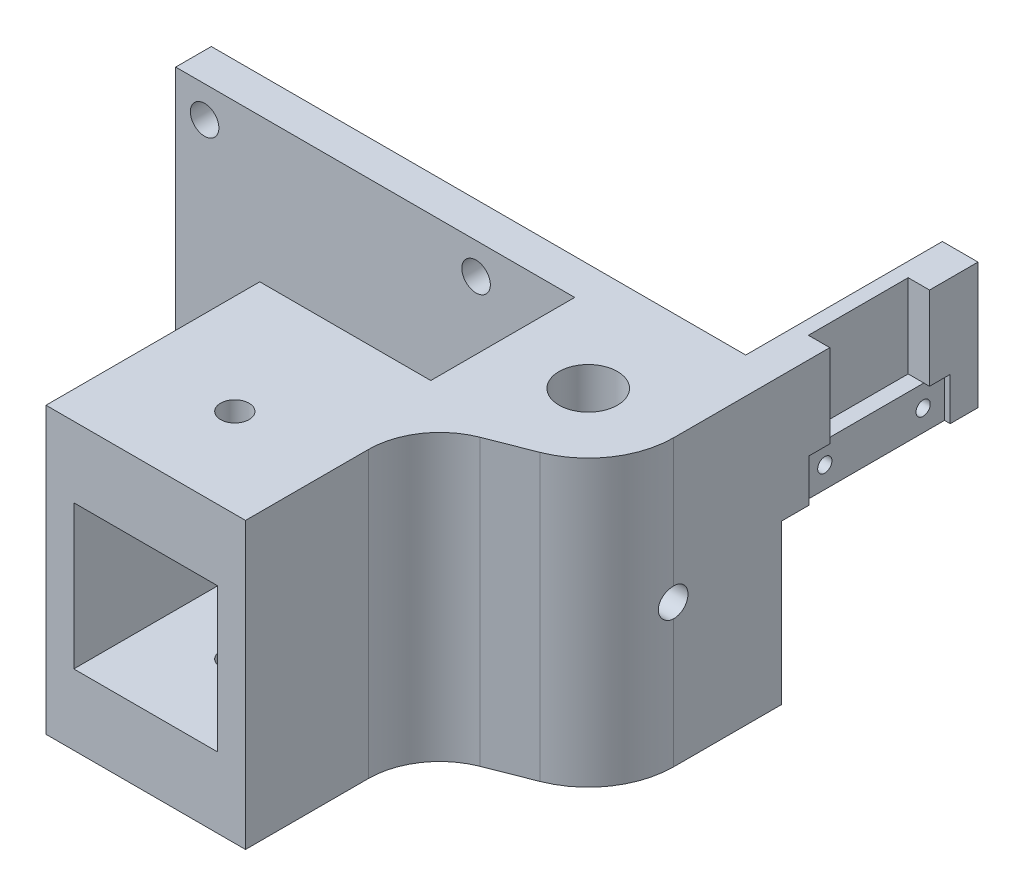
SolidWorks part; units mm, degrees
ref_plane "Front Plane" through (0, 0, 0) normal (0, 0, 1) x (1, 0, 0)
ref_plane "Top Plane" through (0, 0, 0) normal (0, 1, 0) x (1, 0, 0)
ref_plane "Right Plane" through (0, 0, 0) normal (1, 0, 0) x (0, 0, -1)
sketch "Sketch1" plane through (0, 0, 0) normal (0, 1, 0) x (1, 0, 0)
  line L0 (-32, 55.2) -> (-32, 50.2)
  line L1 (-32, 50.2) -> (24, 50.2)
  line L2 (24, 50.2) -> (24, 30)
  line L3 (24, 30) -> (0, 30)
  line L4 (0, 30) -> (0, 0)
  line L5 (0, 0) -> (28, 0)
  line L6 (28, 0) -> (28, 17.2586)
  line L7 (28, 55.2) -> (-32, 55.2)
  line L9 (40.3722, 28.9249) -> (34.3565, 26.5712)
  line L10 (28, 55.2) -> (43, 55.2)
  line L11 (43, 55.2) -> (43, 82.8)
  line L12 (43, 82.8) -> (48, 82.8)
  line L13 (48, 82.8) -> (48, 40.1)
  circle A1 centre (36, 40.1) radius 4.1
  arc A2 (48, 40.1) -> (40.3722, 28.9249) centre (36, 40.1) cw
  arc A3 (28, 17.2586) -> (34.3565, 26.5712) centre (38, 17.2586) cw
  point P18 (24, 40.1)
  point P36 (43, 69)
  dimension "D6" = 8.2
  dimension "D7" = 5
  dimension "D10" = 10
  dimension "D1" = 5
  dimension "D2" = 4
  dimension "D3" = 30
  dimension "D4" = 20.2
  dimension "D5" = 28
  dimension "D8" = 8
  dimension "D9" = 19
  dimension "D11" = 13.8
extrude "Boss-Extrude1" add sketch "Sketch1" along normal blind 40 contours L6 A1 L9 | L6 L7 L0 L1 L2 L3 L4 L5 region at (-2, 0, -54.0487)
sketch "Sketch2" plane through (0, 0, 0) normal (0, 0, 1) x (1, 0, 0)
  line L0 (14, 30.1) -> (14, 9.9) construction
  line L1 (3.9, 30.1) -> (24.1, 30.1)
  line L2 (3.9, 30.1) -> (3.9, 9.9)
  line L3 (3.9, 9.9) -> (24.1, 9.9)
  line L4 (24.1, 30.1) -> (24.1, 9.9)
  line L5 (24.1, 20) -> (3.9, 20) construction
  line L8 (0, 40) -> (0, 0) construction
  line L9 (28, 40) -> (28, 0) construction
  line L10 (0, 40) -> (0, 0) construction
  line L11 (0, 40) -> (0, 0)
  point P10 (0, 20)
  dimension "D1" = 20.2
extrude "Cut-Extrude1" cut sketch "Sketch2" against normal blind 25 contours L4 L1 L2 L3 region at (14, 20, 0)
sketch "Sketch3" plane through (0, 40, 0) normal (0, 1, 0) x (1, 0, 0)
  line L1 (3.9, 25) -> (24.1, 25) construction
  line L2 (14, 25) -> (14, 0) construction
  line L4 (3.9, 25) -> (24.1, 25)
  line L5 (0, 0) -> (28, 0) construction
  circle A0 centre (14, 12.5) radius 2
  dimension "D1" = 4
extrude "Cut-Extrude2" cut sketch "Sketch3" against normal through all contours A0
sketch "Sketch4" plane through (0, 0, -55.2) normal (0, 0, -1) x (-1, 0, 0)
  line L0 (32, 20) -> (-24.602, 20) construction
  line L1 (32, 40) -> (32, 0) construction
  line L2 (-24.602, 40) -> (-24.602, 0) construction
  line L3 (-24, 40) -> (-24, 0) construction
  line L4 (-24, 40) -> (-24, 0)
  circle A0 centre (-10.16, 35.62) radius 2
  circle A1 centre (27.94, 35.62) radius 2
  circle A3 centre (27.94, 4.38) radius 2
  circle A5 centre (-10.16, 4.38) radius 2
  dimension "D5" = 4
  dimension "D3" = 31.24
  dimension "D4" = 38.1
  dimension "D6" = 13.84
  dimension "D1" = 2
  dimension "D2" = 2
extrude "Cut-Extrude3" cut sketch "Sketch4" against normal up to surface (5 mm away) contours A5 | A1 | A3 | A0 up to face at (-4, 20, -50.2)
sketch "Sketch5" plane through (48, 0, 0) normal (1, 0, 0) x (0, 0, -1)
  line L0 (55.2, 40) -> (55.2, 0) construction
  line L1 (55.2, 40) -> (55.2, 0)
  line L2 (55.2, 20) -> (82.8, 20) construction
  line L3 (40.1, 40) -> (40.1, 0) construction
  line L4 (82.8, 40) -> (82.8, 0) construction
  line L6 (76, 22.3) -> (76, 44.3)
  line L7 (62, 22.3) -> (62, 44.3)
  line L8 (76, 44.3) -> (62, 44.3)
  line L9 (69, 26.3055) -> (69, 44.3) construction
  line L10 (75.9, 25.3) -> (62.1, 25.3) construction
  line L11 (59.1, 22.3) -> (59.1, 28.3)
  line L12 (59.1, 22.3) -> (78.9, 22.3)
  line L13 (59.1, 28.3) -> (78.9, 28.3)
  line L14 (78.9, 22.3) -> (78.9, 28.3)
  line L15 (78.9, 25.3) -> (59.1, 25.3) construction
  line L16 (76, 39.3) -> (104.946, 39.3)
  line L17 (55.2, 22.3) -> (87.8946, 22.3)
  circle A1 centre (69, 20) radius 1.5462
  circle A2 centre (75.9, 25.3) radius 1
  circle A3 centre (62.1, 25.3) radius 1
  circle A4 centre (40.1, 20) radius 2
  point P15 (69, 44.3)
  point P16 (69, 20)
  point P34 (40.1, 20)
  line M9 (40.1, 0) -> (82.8, 0)
  line M10 (82.8, 0) -> (82.8, 40)
  line M11 (82.8, 40) -> (40.1, 40)
  dimension "D1" = 2
  dimension "D9" = 4
  dimension "D2" = 13.8
  dimension "D3" = 5.3
  dimension "D4" = 19
  dimension "D5" = 3
  dimension "D6" = 3
  dimension "D7" = 5
  dimension "D8" = 14
extrude "Cut-Extrude4" cut sketch "Sketch5" against normal blind 0.8 contours A3 L7 L12 L6 A2 L13 | A3 L7 L13 L11 L12 | A2 L6 L12 L14 L13 region at (48, 25.3, -77.5416) region at (48, 25.3, -69) region at (48, 25.3, -60.4584)
extrude "Cut-Extrude5" cut sketch "Sketch5<5>" against normal blind 3 contours L7 L13 L6 M11 region at (48, 34.15, -69)
sketch "Sketch5<5>" plane through (48, 0, 0) normal (1, 0, 0) x (0, 0, -1) same geometry as "Sketch5"
extrude "Cut-Extrude6" cut sketch "Sketch5<6>" against normal up to next contours L17 L1 L12 A1 M9 M10 | A3 | A2 | A1 | A4 region at (48, 11.0407, -69)
sketch "Sketch5<6>" plane through (48, 0, 0) normal (1, 0, 0) x (0, 0, -1) same geometry as "Sketch5"
equation "\"local_angle\"=58.9479"
